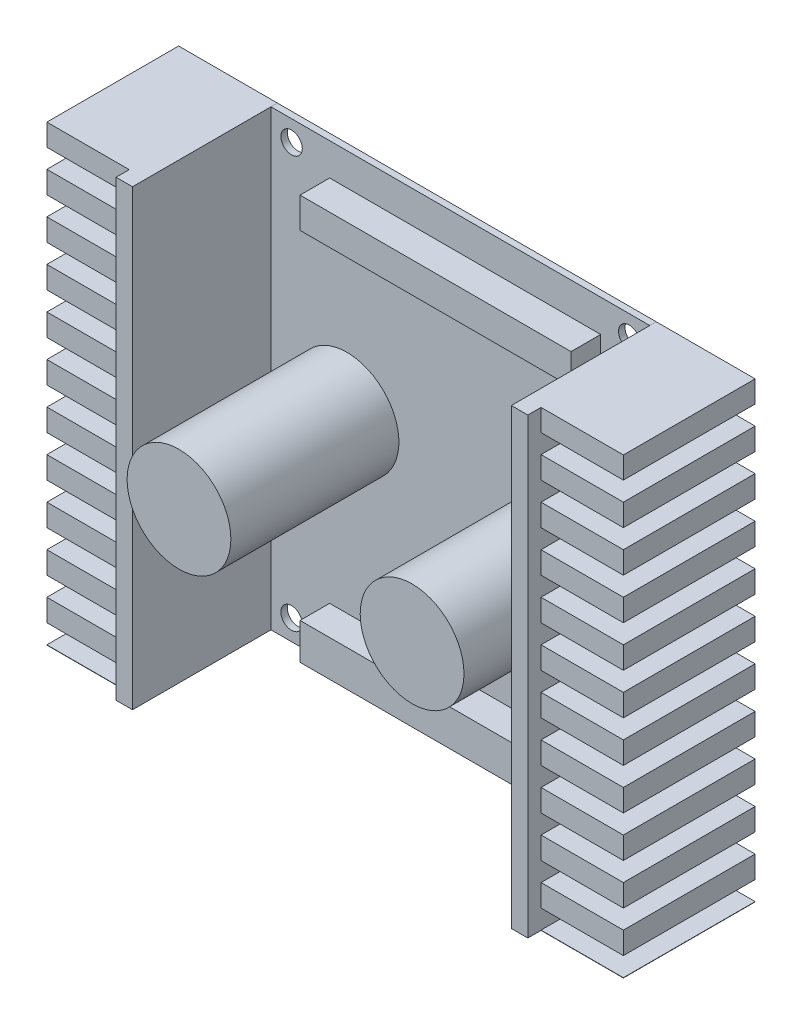
SolidWorks part; units mm, degrees
ref_plane "Front Plane" through (0, 0, 0) normal (0, 0, 1) x (1, 0, 0)
ref_plane "Top Plane" through (0, 0, 0) normal (0, 1, 0) x (1, 0, 0)
ref_plane "Right Plane" through (0, 0, 0) normal (1, 0, 0) x (0, 0, -1)
sketch "Sketch1" plane through (0, 0, 0) normal (0, 0, 1) x (1, 0, 0)
  line L0 (0, 37.0522) -> (0, -37.9104) construction
  line L1 (-29.21, -34.925) -> (29.21, -34.925)
  line L2 (-29.21, -34.925) -> (-29.21, 34.925)
  line L3 (-29.21, 34.925) -> (29.21, 34.925)
  line L4 (29.21, -34.925) -> (29.21, 34.925)
  line L5 (-29.21, -34.925) -> (29.21, 34.925) construction
  line L6 (-29.21, 34.925) -> (29.21, -34.925) construction
  circle A0 centre (-26.035, 31.75) radius 1.651
  circle A1 centre (-26.035, -31.75) radius 1.651
  circle A2 centre (26.035, -31.75) radius 1.651
  circle A3 centre (26.035, 31.75) radius 1.651
  point P0 (0, 0)
  dimension "D3" = 3.302
  dimension "D4" = 3.302
  dimension "D1" = 58.42
  dimension "D2" = 69.85
  dimension "D5" = 63.5
  dimension "D6" = 3.175
  dimension "D7" = 3.175
extrude "Boss-Extrude1" add sketch "Sketch1" along normal blind 1
sketch "Sketch2" plane through (0, 0, 0) normal (0, 0, -1) x (-1, 0, 0)
  line L0 (-29.21, 34.925) -> (29.21, 34.925) construction
  line L1 (44.45, -34.925) -> (-44.45, -34.925)
  line L2 (44.45, -34.925) -> (44.45, 34.925)
  line L3 (44.45, 34.925) -> (-44.45, 34.925)
  line L4 (-44.45, -34.925) -> (-44.45, 34.925)
  line L5 (44.45, -34.925) -> (-44.45, 34.925) construction
  line L6 (44.45, 34.925) -> (-44.45, -34.925) construction
  line L7 (31.75, -34.925) -> (-31.75, -34.925)
  line L8 (31.75, -34.925) -> (31.75, 34.925)
  line L9 (31.75, 34.925) -> (-31.75, 34.925)
  line L10 (-31.75, -34.925) -> (-31.75, 34.925)
  line L11 (31.75, -34.925) -> (-31.75, 34.925) construction
  line L12 (31.75, 34.925) -> (-31.75, -34.925) construction
  point P0 (0, 0)
  point P6 (0, 0)
  line M5 (-29.21, 34.925) -> (-29.21, -34.925)
  line M7 (29.21, -34.925) -> (29.21, 34.925)
  dimension "D1" = 88.9
  dimension "D2" = 63.5
extrude "Boss-Extrude2" add sketch "Sketch2" against normal blind 22.352 separate body contours L1 L8 L3 M7 | L10 L1 L3 M5 region at (-30.48, 0, 0) region at (30.48, 0, 0)
extrude "Boss-Extrude3" add sketch "Sketch2<3>" against normal blind 20.32 contours L8 L1 L2 L3 | L1 L10 L3 L4 region at (-38.1, 0, 0) region at (38.1, 0, 0)
sketch "Sketch2<3>" plane through (0, 0, 0) normal (0, 0, -1) x (-1, 0, 0) same geometry as "Sketch2"
ref_plane "Plane1" through (0, 0, 22.352) normal (0, 0, 1) x (1, 0, 0)
sketch "Sketch3" plane through (0, 0, 22.352) normal (0, 0, 1) x (1, 0, 0)
  line L0 (-44.45, -34.925) -> (-44.45, 34.925) construction
  line L1 (-31.75, 34.925) -> (-44.45, 34.925)
  line L2 (-31.75, 34.925) -> (-31.75, 31.5634)
  line L3 (-31.75, 31.5634) -> (-44.45, 31.5634)
  line L4 (-44.45, 34.925) -> (-44.45, 31.5634)
  line L5 (-31.75, 31.5634) -> (-31.75, 28.6204)
  line L6 (-31.75, -34.925) -> (-31.75, 34.925) construction
  line L7 (-31.75, 28.6204) -> (-44.45, 28.6204)
  line L8 (-44.45, 28.6204) -> (-44.45, 31.5634)
  line L9 (-31.75, 22.2704) -> (-44.45, 22.2704)
  line L10 (-31.75, 25.2134) -> (-44.45, 25.2134)
  line L11 (-31.75, 25.2134) -> (-31.75, 22.2704)
  line L12 (-44.45, 22.2704) -> (-44.45, 25.2134)
  line L13 (-31.75, 15.9204) -> (-44.45, 15.9204)
  line L14 (-31.75, 18.8634) -> (-44.45, 18.8634)
  line L15 (-31.75, 18.8634) -> (-31.75, 15.9204)
  line L16 (-44.45, 15.9204) -> (-44.45, 18.8634)
  line L17 (-31.75, 9.5704) -> (-44.45, 9.5704)
  line L18 (-31.75, 12.5134) -> (-44.45, 12.5134)
  line L19 (-31.75, 12.5134) -> (-31.75, 9.5704)
  line L20 (-44.45, 9.5704) -> (-44.45, 12.5134)
  line L21 (-31.75, 3.2204) -> (-44.45, 3.2204)
  line L22 (-31.75, 6.1634) -> (-44.45, 6.1634)
  line L23 (-31.75, 6.1634) -> (-31.75, 3.2204)
  line L24 (-44.45, 3.2204) -> (-44.45, 6.1634)
  line L25 (-31.75, -3.1296) -> (-44.45, -3.1296)
  line L26 (-31.75, -0.1866) -> (-44.45, -0.1866)
  line L27 (-31.75, -0.1866) -> (-31.75, -3.1296)
  line L28 (-44.45, -3.1296) -> (-44.45, -0.1866)
  line L29 (-31.75, -9.4796) -> (-44.45, -9.4796)
  line L30 (-31.75, -6.5366) -> (-44.45, -6.5366)
  line L31 (-31.75, -6.5366) -> (-31.75, -9.4796)
  line L32 (-44.45, -9.4796) -> (-44.45, -6.5366)
  line L33 (-31.75, -15.8296) -> (-44.45, -15.8296)
  line L34 (-31.75, -12.8866) -> (-44.45, -12.8866)
  line L35 (-31.75, -12.8866) -> (-31.75, -15.8296)
  line L36 (-44.45, -15.8296) -> (-44.45, -12.8866)
  line L37 (-31.75, -22.1796) -> (-44.45, -22.1796)
  line L38 (-31.75, -19.2366) -> (-44.45, -19.2366)
  line L39 (-31.75, -19.2366) -> (-31.75, -22.1796)
  line L40 (-44.45, -22.1796) -> (-44.45, -19.2366)
  line L41 (-31.75, -28.5296) -> (-44.45, -28.5296)
  line L42 (-31.75, -25.5866) -> (-44.45, -25.5866)
  line L43 (-31.75, -25.5866) -> (-31.75, -28.5296)
  line L44 (-44.45, -28.5296) -> (-44.45, -25.5866)
  line L45 (-31.75, -34.8796) -> (-44.45, -34.8796)
  line L46 (-31.75, -31.9366) -> (-44.45, -31.9366)
  line L47 (-31.75, -31.9366) -> (-31.75, -34.8796)
  line L48 (-44.45, -34.8796) -> (-44.45, -31.9366)
  line L49 (0, 41.1942) -> (0, -42.651) construction
  line L50 (44.45, -34.8796) -> (44.45, -31.9366)
  line L51 (31.75, -31.9366) -> (31.75, -34.8796)
  line L52 (31.75, -31.9366) -> (44.45, -31.9366)
  line L53 (31.75, -34.8796) -> (44.45, -34.8796)
  line L54 (44.45, -28.5296) -> (44.45, -25.5866)
  line L55 (31.75, -25.5866) -> (31.75, -28.5296)
  line L56 (31.75, -25.5866) -> (44.45, -25.5866)
  line L57 (31.75, -28.5296) -> (44.45, -28.5296)
  line L58 (44.45, -22.1796) -> (44.45, -19.2366)
  line L59 (31.75, -19.2366) -> (31.75, -22.1796)
  line L60 (31.75, -19.2366) -> (44.45, -19.2366)
  line L61 (31.75, -22.1796) -> (44.45, -22.1796)
  line L62 (44.45, -15.8296) -> (44.45, -12.8866)
  line L63 (31.75, -12.8866) -> (31.75, -15.8296)
  line L64 (31.75, -12.8866) -> (44.45, -12.8866)
  line L65 (31.75, -15.8296) -> (44.45, -15.8296)
  line L66 (44.45, -9.4796) -> (44.45, -6.5366)
  line L67 (31.75, -6.5366) -> (31.75, -9.4796)
  line L68 (31.75, -6.5366) -> (44.45, -6.5366)
  line L69 (31.75, -9.4796) -> (44.45, -9.4796)
  line L70 (44.45, -3.1296) -> (44.45, -0.1866)
  line L71 (31.75, -0.1866) -> (31.75, -3.1296)
  line L72 (31.75, -0.1866) -> (44.45, -0.1866)
  line L73 (31.75, -3.1296) -> (44.45, -3.1296)
  line L74 (44.45, 3.2204) -> (44.45, 6.1634)
  line L75 (31.75, 6.1634) -> (31.75, 3.2204)
  line L76 (31.75, 6.1634) -> (44.45, 6.1634)
  line L77 (31.75, 3.2204) -> (44.45, 3.2204)
  line L78 (44.45, 9.5704) -> (44.45, 12.5134)
  line L79 (31.75, 12.5134) -> (31.75, 9.5704)
  line L80 (31.75, 12.5134) -> (44.45, 12.5134)
  line L81 (31.75, 9.5704) -> (44.45, 9.5704)
  line L82 (44.45, 15.9204) -> (44.45, 18.8634)
  line L83 (31.75, 18.8634) -> (31.75, 15.9204)
  line L84 (31.75, 18.8634) -> (44.45, 18.8634)
  line L85 (31.75, 15.9204) -> (44.45, 15.9204)
  line L86 (44.45, 22.2704) -> (44.45, 25.2134)
  line L87 (31.75, 25.2134) -> (31.75, 22.2704)
  line L88 (31.75, 25.2134) -> (44.45, 25.2134)
  line L89 (31.75, 22.2704) -> (44.45, 22.2704)
  line L90 (44.45, 28.6204) -> (44.45, 31.5634)
  line L91 (31.75, 28.6204) -> (44.45, 28.6204)
  line L92 (31.75, 31.5634) -> (31.75, 28.6204)
  line L93 (44.45, 34.925) -> (44.45, 31.5634)
  line L94 (31.75, 31.5634) -> (44.45, 31.5634)
  line L95 (31.75, 34.925) -> (31.75, 31.5634)
  line L96 (31.75, 34.925) -> (44.45, 34.925)
  dimension "D1" = 11
extrude "Cut-Extrude3" cut sketch "Sketch3" against normal blind 37.084 contours L8 L7 L5 L3 | L12 L9 L11 L10 | L16 L13 L15 L14 | L20 L17 L19 L18 | L24 L21 L23 L22 | L32 L29 L31 L30 | L36 L33 L35 L34 | L40 L37 L39 L38 | L44 L41 L43 L42 | L51 L53 L50 L52 | L55 L57 L54 L56 | L59 L61 L58 L60 | L71 L73 L70 L72 | L75 L77 L74 L76 | L79 L81 L78 L80 | L83 L85 L82 L84 | L94 L92 L91 L90 | L25 L28 L26 L27 | L45 L48 L46 L47 | L64 L62 L65 L63 | L68 L66 L69 L67 | L89 L86 L88 L87 region at (-38.1, 30.0919, 22.352) region at (-38.1, 23.7419, 22.352) region at (-38.1, 17.3919, 22.352) region at (-38.1, 11.0419, 22.352) region at (-38.1, 4.6919, 22.352) region at (-38.1, -8.0081, 22.352) region at (-38.1, -14.3581, 22.352) region at (-38.1, -20.7081, 22.352) region at (-38.1, -27.0581, 22.352) region at (38.1, -33.4081, 22.352) region at (38.1, -27.0581, 22.352) region at (38.1, -20.7081, 22.352) region at (38.1, -1.6581, 22.352) region at (38.1, 4.6919, 22.352) region at (38.1, 11.0419, 22.352) region at (38.1, 17.3919, 22.352) region at (38.1, 30.0919, 22.352)
sketch "Sketch4" plane through (0, 0, 1) normal (0, 0, 1) x (1, 0, 0)
  circle A0 centre (-17.4865, 0) radius 8.001
  circle A1 centre (18.458, 0) radius 8.001
  point P4 (-14.1835, 0)
  point P5 (16.515, 0)
  point P6 (-17.4865, 0)
  point P7 (0, 0)
  point P8 (18.458, 0)
  dimension "D1" = 16.002
extrude "Boss-Extrude4" add sketch "Sketch4" along normal blind 25.908
sketch "Sketch5" plane through (0, 0, 1) normal (0, 0, 1) x (1, 0, 0)
  line L1 (-20.1593, 29.9447) -> (21.6308, 29.9447)
  line L2 (-20.1593, 29.9447) -> (-20.1593, 25.236)
  line L3 (-20.1593, 25.236) -> (21.6308, 25.236)
  line L4 (21.6308, 29.9447) -> (21.6308, 25.236)
  line L5 (-20.1593, -26.8546) -> (21.6308, -26.8546)
  line L6 (-20.1593, -26.8546) -> (-20.1593, -32.4462)
  line L7 (-20.1593, -32.4462) -> (21.6308, -32.4462)
  line L8 (21.6308, -26.8546) -> (21.6308, -32.4462)
extrude "Boss-Extrude5" add sketch "Sketch5" along normal blind 4.572
